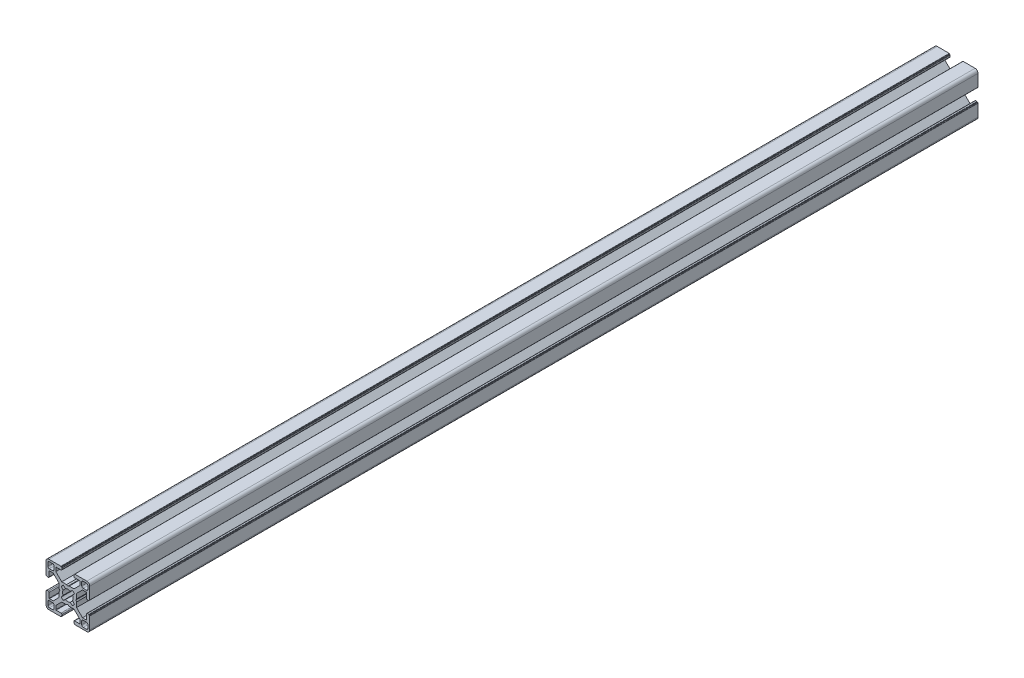
SolidWorks part; units mm, degrees
material "6061 Alloy"
ref_plane "Front" through (0, 0, 0) normal (0, 0, 1) x (1, 0, 0)
ref_plane "Top" through (0, 0, 0) normal (0, 1, 0) x (1, 0, 0)
ref_plane "Right" through (0, 0, 0) normal (1, 0, 0) x (0, 0, -1)
sketch "Sketch1" plane through (0, 0, 0) normal (0, 0, 1) x (1, 0, 0)
  line L0 (13.7, 12.7) -> (13.7, 10.5)
  line L1 (10.5, 9.5) -> (12.7, 9.5)
  line L2 (9.5, 12.7) -> (9.5, 10.5)
  line L3 (10.5, 13.7) -> (12.7, 13.7)
  line L4 (3.1359, 4.5184) -> (1.6001, 3.2806)
  line L5 (3.2806, 1.6001) -> (4.5053, 3.1547)
  line L6 (6.0045, 0.9) -> (5.4849, 0)
  line L7 (6.0045, 4.2045) -> (6.0045, 0.9)
  line L8 (0, -5.4849) -> (0.9, -6)
  line L9 (0.9, -6) -> (4.2045, -6)
  line L10 (4.2045, -6) -> (8.25, -10.05)
  line L11 (8.25, -10.05) -> (8.25, -12.6)
  line L12 (4.65, -12.8) -> (8.05, -12.8)
  line L13 (4.05, -14.3) -> (4.05, -13.4)
  line L14 (4.25, -14.5) -> (4.35, -14.5)
  line L15 (4.55, -14.8) -> (4.55, -14.7)
  line L16 (4.75, -15) -> (13, -15)
  line L17 (15, -13) -> (15, -4.75)
  line L18 (14.7, -4.55) -> (14.8, -4.55)
  line L19 (14.5, -4.35) -> (14.5, -4.25)
  line L20 (13.4, -4.05) -> (14.3, -4.05)
  line L21 (12.8, -8.05) -> (12.8, -4.65)
  line L22 (12.6, -8.25) -> (10.05, -8.25)
  line L23 (10.05, -8.25) -> (6.0045, -4.2045)
  line L24 (6.0045, -4.2045) -> (6.0045, -0.9)
  line L25 (6.0045, -0.9) -> (5.4849, 0)
  line L26 (10.05, 8.25) -> (6.0045, 4.2045)
  line L27 (12.6, 8.25) -> (10.05, 8.25)
  line L28 (12.8, 8.05) -> (12.8, 4.65)
  line L29 (13.4, 4.05) -> (14.3, 4.05)
  line L30 (14.5, 4.35) -> (14.5, 4.25)
  line L31 (14.7, 4.55) -> (14.8, 4.55)
  line L32 (15, 13) -> (15, 4.75)
  line L33 (4.75, 15) -> (13, 15)
  line L34 (4.55, 14.8) -> (4.55, 14.7)
  line L35 (4.25, 14.5) -> (4.35, 14.5)
  line L36 (4.05, 14.3) -> (4.05, 13.4)
  line L37 (4.65, 12.8) -> (8.05, 12.8)
  line L38 (8.25, 10.05) -> (8.25, 12.6)
  line L39 (4.2045, 6) -> (8.25, 10.05)
  line L40 (0.9, 6) -> (4.2045, 6)
  line L41 (0, 5.4849) -> (0.9, 6)
  line L42 (-13.7, -12.7) -> (-13.7, -10.5)
  line L43 (-10.5, -9.5) -> (-12.7, -9.5)
  line L44 (-9.5, -12.7) -> (-9.5, -10.5)
  line L45 (-10.5, -13.7) -> (-12.7, -13.7)
  line L46 (-3.1359, -4.5184) -> (-1.6001, -3.2806)
  line L47 (-3.2806, -1.6001) -> (-4.5053, -3.1547)
  line L48 (0, 5.4849) -> (-0.9, 6)
  line L49 (-0.9, 6) -> (-4.2045, 6)
  line L50 (-4.2045, 6) -> (-8.25, 10.05)
  line L51 (-8.25, 10.05) -> (-8.25, 12.6)
  line L52 (-4.65, 12.8) -> (-8.05, 12.8)
  line L53 (-4.05, 14.3) -> (-4.05, 13.4)
  line L54 (-4.25, 14.5) -> (-4.35, 14.5)
  line L55 (-4.55, 14.8) -> (-4.55, 14.7)
  line L56 (-4.75, 15) -> (-13, 15)
  line L57 (-15, 13) -> (-15, 4.75)
  line L58 (-14.7, 4.55) -> (-14.8, 4.55)
  line L59 (-14.5, 4.35) -> (-14.5, 4.25)
  line L60 (-13.4, 4.05) -> (-14.3, 4.05)
  line L61 (-12.8, 8.05) -> (-12.8, 4.65)
  line L62 (-12.6, 8.25) -> (-10.05, 8.25)
  line L63 (-10.05, 8.25) -> (-6.0045, 4.2045)
  line L64 (-6.0045, -0.9) -> (-5.4849, 0)
  line L65 (-6.0045, -4.2045) -> (-6.0045, -0.9)
  line L66 (-10.05, -8.25) -> (-6.0045, -4.2045)
  line L67 (-12.6, -8.25) -> (-10.05, -8.25)
  line L68 (-12.8, -8.05) -> (-12.8, -4.65)
  line L69 (-13.4, -4.05) -> (-14.3, -4.05)
  line L70 (-14.5, -4.35) -> (-14.5, -4.25)
  line L71 (-14.7, -4.55) -> (-14.8, -4.55)
  line L72 (-15, -13) -> (-15, -4.75)
  line L73 (-4.75, -15) -> (-13, -15)
  line L74 (-4.55, -14.8) -> (-4.55, -14.7)
  line L75 (-4.25, -14.5) -> (-4.35, -14.5)
  line L76 (-4.05, -14.3) -> (-4.05, -13.4)
  line L77 (3.2806, -1.6001) -> (4.5053, -3.1547)
  line L78 (3.1359, -4.5184) -> (1.6001, -3.2806)
  line L79 (-4.65, -12.8) -> (-8.05, -12.8)
  line L80 (-8.25, -10.05) -> (-8.25, -12.6)
  line L81 (-4.2045, -6) -> (-8.25, -10.05)
  line L82 (-0.9, -6) -> (-4.2045, -6)
  line L83 (0, -5.4849) -> (-0.9, -6)
  line L84 (10.5, -13.7) -> (12.7, -13.7)
  line L85 (9.5, -12.7) -> (9.5, -10.5)
  line L86 (10.5, -9.5) -> (12.7, -9.5)
  line L87 (13.7, -12.7) -> (13.7, -10.5)
  line L88 (-6.0045, 4.2045) -> (-6.0045, 0.9)
  line L89 (-6.0045, 0.9) -> (-5.4849, 0)
  line L90 (-3.2806, 1.6001) -> (-4.5053, 3.1547)
  line L91 (-3.1359, 4.5184) -> (-1.6001, 3.2806)
  line L92 (-10.5, 13.7) -> (-12.7, 13.7)
  line L93 (-9.5, 12.7) -> (-9.5, 10.5)
  line L94 (-10.5, 9.5) -> (-12.7, 9.5)
  line L95 (-13.7, 12.7) -> (-13.7, 10.5)
  line L96 (-23.4857, 0) -> (20.9308, 0) construction
  line L97 (0, 17.9563) -> (0, -17.361) construction
  arc A0 (13.7, 12.7) -> (12.7, 13.7) centre (12.7, 12.7) ccw
  arc A1 (12.7, 9.5) -> (13.7, 10.5) centre (12.7, 10.5) ccw
  arc A2 (9.5, 10.5) -> (10.5, 9.5) centre (10.5, 10.5) ccw
  arc A3 (10.5, 13.7) -> (9.5, 12.7) centre (10.5, 12.7) ccw
  arc A4 (1.6001, 3.2806) -> (-1.6001, 3.2806) centre (0, 0) ccw
  arc A5 (8.25, -12.6) -> (8.05, -12.8) centre (8.05, -12.6) cw
  arc A6 (4.65, -12.8) -> (4.05, -13.4) centre (4.65, -13.4) ccw
  arc A7 (4.05, -14.3) -> (4.25, -14.5) centre (4.25, -14.3) ccw
  arc A8 (4.35, -14.5) -> (4.55, -14.7) centre (4.35, -14.7) cw
  arc A9 (4.55, -14.8) -> (4.75, -15) centre (4.75, -14.8) ccw
  arc A10 (13, -15) -> (15, -13) centre (13, -13) ccw
  arc A11 (15, -4.75) -> (14.8, -4.55) centre (14.8, -4.75) ccw
  arc A12 (14.7, -4.55) -> (14.5, -4.35) centre (14.7, -4.35) cw
  arc A13 (14.5, -4.25) -> (14.3, -4.05) centre (14.3, -4.25) ccw
  arc A14 (13.4, -4.05) -> (12.8, -4.65) centre (13.4, -4.65) ccw
  arc A15 (12.8, -8.05) -> (12.6, -8.25) centre (12.6, -8.05) cw
  arc A16 (4.5053, 3.1547) -> (3.1359, 4.5184) centre (0, 0) ccw
  arc A17 (12.8, 8.05) -> (12.6, 8.25) centre (12.6, 8.05) ccw
  arc A18 (13.4, 4.05) -> (12.8, 4.65) centre (13.4, 4.65) cw
  arc A19 (14.5, 4.25) -> (14.3, 4.05) centre (14.3, 4.25) cw
  arc A20 (14.7, 4.55) -> (14.5, 4.35) centre (14.7, 4.35) ccw
  arc A21 (15, 4.75) -> (14.8, 4.55) centre (14.8, 4.75) cw
  arc A22 (13, 15) -> (15, 13) centre (13, 13) cw
  arc A23 (4.55, 14.8) -> (4.75, 15) centre (4.75, 14.8) cw
  arc A24 (4.35, 14.5) -> (4.55, 14.7) centre (4.35, 14.7) ccw
  arc A25 (4.05, 14.3) -> (4.25, 14.5) centre (4.25, 14.3) cw
  arc A26 (4.65, 12.8) -> (4.05, 13.4) centre (4.65, 13.4) cw
  arc A27 (8.25, 12.6) -> (8.05, 12.8) centre (8.05, 12.6) ccw
  arc A28 (-13.7, -12.7) -> (-12.7, -13.7) centre (-12.7, -12.7) ccw
  arc A29 (-12.7, -9.5) -> (-13.7, -10.5) centre (-12.7, -10.5) ccw
  arc A30 (-9.5, -10.5) -> (-10.5, -9.5) centre (-10.5, -10.5) ccw
  arc A31 (-10.5, -13.7) -> (-9.5, -12.7) centre (-10.5, -12.7) ccw
  arc A32 (-4.5053, -3.1547) -> (-3.1359, -4.5184) centre (0, 0) ccw
  arc A33 (-3.2806, 1.6001) -> (-3.2806, -1.6001) centre (0, 0) ccw
  arc A34 (-8.25, 12.6) -> (-8.05, 12.8) centre (-8.05, 12.6) cw
  arc A35 (-4.65, 12.8) -> (-4.05, 13.4) centre (-4.65, 13.4) ccw
  arc A36 (-4.05, 14.3) -> (-4.25, 14.5) centre (-4.25, 14.3) ccw
  arc A37 (-4.35, 14.5) -> (-4.55, 14.7) centre (-4.35, 14.7) cw
  arc A38 (-4.55, 14.8) -> (-4.75, 15) centre (-4.75, 14.8) ccw
  arc A39 (-13, 15) -> (-15, 13) centre (-13, 13) ccw
  arc A40 (-15, 4.75) -> (-14.8, 4.55) centre (-14.8, 4.75) ccw
  arc A41 (-14.7, 4.55) -> (-14.5, 4.35) centre (-14.7, 4.35) cw
  arc A42 (-14.5, 4.25) -> (-14.3, 4.05) centre (-14.3, 4.25) ccw
  arc A43 (-13.4, 4.05) -> (-12.8, 4.65) centre (-13.4, 4.65) ccw
  arc A44 (-12.8, 8.05) -> (-12.6, 8.25) centre (-12.6, 8.05) cw
  arc A45 (-4.5053, 3.1547) -> (-3.1359, 4.5184) centre (0, 0) cw
  arc A46 (-12.8, -8.05) -> (-12.6, -8.25) centre (-12.6, -8.05) ccw
  arc A47 (-13.4, -4.05) -> (-12.8, -4.65) centre (-13.4, -4.65) cw
  arc A48 (-14.5, -4.25) -> (-14.3, -4.05) centre (-14.3, -4.25) cw
  arc A49 (3.2806, 1.6001) -> (3.2806, -1.6001) centre (0, 0) cw
  arc A50 (4.5053, -3.1547) -> (3.1359, -4.5184) centre (0, 0) cw
  arc A51 (1.6001, -3.2806) -> (-1.6001, -3.2806) centre (0, 0) cw
  arc A52 (-14.7, -4.55) -> (-14.5, -4.35) centre (-14.7, -4.35) ccw
  arc A53 (-15, -4.75) -> (-14.8, -4.55) centre (-14.8, -4.75) cw
  arc A54 (-13, -15) -> (-15, -13) centre (-13, -13) cw
  arc A55 (-4.55, -14.8) -> (-4.75, -15) centre (-4.75, -14.8) cw
  arc A56 (10.5, -13.7) -> (9.5, -12.7) centre (10.5, -12.7) cw
  arc A57 (9.5, -10.5) -> (10.5, -9.5) centre (10.5, -10.5) cw
  arc A58 (12.7, -9.5) -> (13.7, -10.5) centre (12.7, -10.5) cw
  arc A59 (13.7, -12.7) -> (12.7, -13.7) centre (12.7, -12.7) cw
  arc A60 (-4.35, -14.5) -> (-4.55, -14.7) centre (-4.35, -14.7) ccw
  arc A61 (-4.05, -14.3) -> (-4.25, -14.5) centre (-4.25, -14.3) cw
  arc A62 (-4.65, -12.8) -> (-4.05, -13.4) centre (-4.65, -13.4) cw
  arc A63 (-8.25, -12.6) -> (-8.05, -12.8) centre (-8.05, -12.6) ccw
  arc A64 (-10.5, 13.7) -> (-9.5, 12.7) centre (-10.5, 12.7) cw
  arc A65 (-9.5, 10.5) -> (-10.5, 9.5) centre (-10.5, 10.5) cw
  arc A66 (-12.7, 9.5) -> (-13.7, 10.5) centre (-12.7, 10.5) cw
  arc A67 (-13.7, 12.7) -> (-12.7, 13.7) centre (-12.7, 12.7) cw
  point P81 (15, 15)
  point P82 (0, 15)
  point P203 (0, -15)
  point P204 (15, -15)
  point P206 (0, 0)
  point P207 (15, 0)
  point P219 (-15, 0)
  point P220 (-15, -15)
  point P221 (-15, 15)
  dimension "D6" = 7.3
  dimension "D7" = 11
  dimension "D1" = 30
  dimension "D2" = 15
  dimension "D3" = 30
  dimension "D4" = 8.1
  dimension "D5" = 9
  dimension "D8" = 8.1
extrude "Boss-Extrude1" add sketch "Sketch1" along normal blind 609.6
